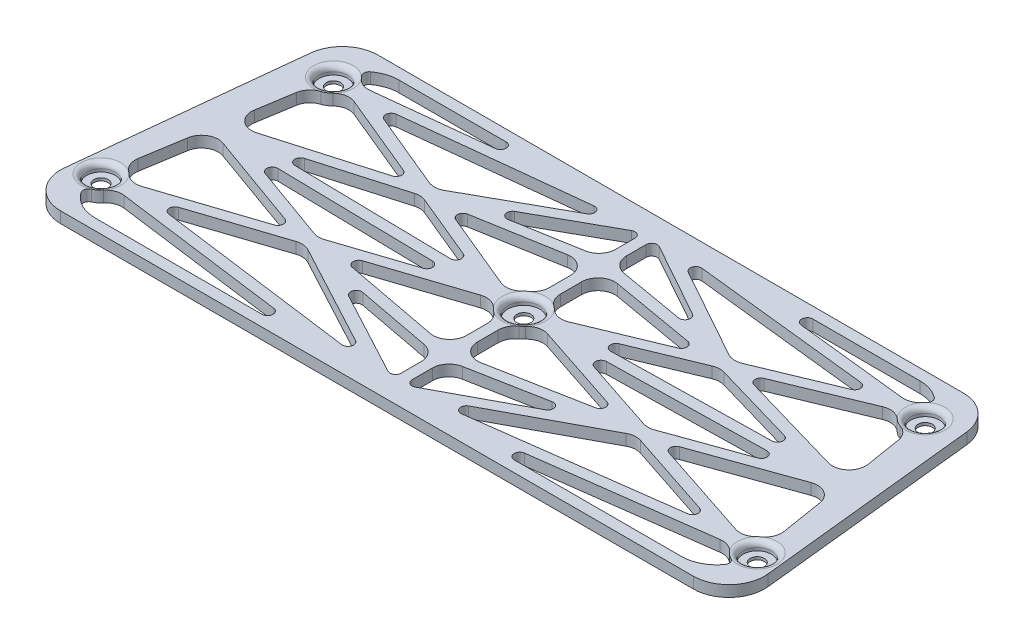
SolidWorks part; units mm, degrees
ref_plane "Front Plane" through (0, 0, 0) normal (0, 0, 1) x (1, 0, 0)
ref_plane "Top Plane" through (0, 0, 0) normal (0, 1, 0) x (1, 0, 0)
ref_plane "Right Plane" through (0, 0, 0) normal (1, 0, 0) x (0, 0, -1)
sketch "Sketch1" plane through (0, 0, 0) normal (0, 1, 0) x (1, 0, 0)
  line L0 (-101.6, -41.91) -> (-92.71, 41.91)
  line L1 (-101.6, -41.91) -> (101.6, -41.91)
  line L2 (-101.6, -41.91) -> (-101.6, 41.91)
  line L3 (-101.6, 41.91) -> (101.6, 41.91)
  line L4 (101.6, -41.91) -> (101.6, 41.91)
  line L5 (-101.6, -41.91) -> (101.6, 41.91) construction
  line L6 (-101.6, 41.91) -> (101.6, -41.91) construction
  line L7 (0, 41.91) -> (0, -41.91) construction
  line L8 (101.6, -41.91) -> (92.71, 41.91)
  circle A0 centre (0, 0) radius 2.032
  circle A1 centre (-93.6752, -27.0205) radius 2.032
  circle A2 centre (-84.4677, 30.1295) radius 2.032
  circle A3 centre (93.6752, -27.0205) radius 2.032
  circle A4 centre (84.4677, 30.1295) radius 2.032
  point P0 (0, 0)
  dimension "D1" = 4.064
  dimension "D6" = 4.064
  dimension "D2" = 203.2
  dimension "D3" = 83.82
  dimension "D4" = 8.89
  dimension "D5" = 83.946
  dimension "D7" = 14.8895
  dimension "D8" = 7.9248
  dimension "D9" = 57.15
  dimension "D10" = 9.2075
extrude "platw" add sketch "Sketch1" along normal blind 3.175 contours L1 L8 L3 L0 A3 A2 A1 A0 A4 region at (-94.9692, 0, 0.2318)
fillet "Fillet1" radius 10.16 2 edges at (101.6, 1.5875, 41.91) (-101.6, 1.5875, 41.91)
fillet "Fillet2" radius 10.16 2 edges at (-92.71, 1.5875, -41.91) (92.71, 1.5875, -41.91)
sketch "Sketch2" plane through (0, 3.175, 0) normal (0, 1, 0) x (1, 0, 0)
  circle A0 centre (-84.4677, 30.1295) radius 4.064
  circle A1 centre (-93.6752, -27.0205) radius 4.064
  circle A2 centre (93.6752, -27.0205) radius 4.064
  circle A3 centre (84.4677, 30.1295) radius 4.064
  circle A4 centre (0, 0) radius 4.572
  dimension "D1" = 8.128
  dimension "D2" = 9.144
extrude "countersinks" cut sketch "Sketch2" against normal blind 2.3813
sketch "Sketch3" plane through (0, 3.175, 0) normal (0, 1, 0) x (1, 0, 0)
  line L0 (-88.0237, -27.0205) -> (-6.1595, 0) construction
  line L1 (-47.0916, -13.5103) -> (-89.0714, 1.5545) construction
  line L2 (-88.0237, -27.0205) -> (0, -38.735) construction
  line L3 (-47.0916, -13.5103) -> (0, -22.4472) construction
  line L4 (-84.4677, 30.1295) -> (-93.6752, -27.0205)
  line L5 (-83.697, -38.735) -> (83.697, -38.735)
  line L6 (93.6752, -27.0205) -> (84.4677, 30.1295)
  line L7 (-74.3648, 38.735) -> (74.3648, 38.735)
  line L8 (-90.3054, -41.91) -> (90.3054, -41.91) construction
  line L9 (-83.5706, 41.91) -> (83.5706, 41.91) construction
  line L10 (-78.8162, 30.1295) -> (-6.1595, 0) construction
  line L11 (-47.0916, -13.5103) -> (0, -38.735) construction
  line L12 (-89.3283, -0.04) -> (-51.9664, -13.4475)
  line L13 (0, -38.735) -> (0, -6.1595)
  line L14 (0, 6.1595) -> (0, 38.735)
  line L15 (-78.8162, 30.1295) -> (0, 38.735) construction
  line L16 (0, 22.4473) -> (-42.4878, 15.0647) construction
  line L17 (-42.4878, 15.0647) -> (0, 38.735) construction
  line L18 (-6.1595, 0) -> (-89.0714, 1.5545) construction
  line L19 (-89.0714, 1.5545) -> (-42.4878, 15.0647) construction
  line L20 (-51.9664, -13.4475) -> (-88.2537, -25.4247)
  line L21 (-79.4439, -0.2138) -> (-47.07, -11.8314)
  line L22 (-47.07, -11.8314) -> (-15.5041, -1.4126)
  line L23 (-15.5041, -1.4126) -> (-79.4439, -0.2138)
  line L24 (-40.7674, -13.0946) -> (-5.9476, -1.6018)
  line L25 (-40.7674, -13.0946) -> (-1.5875, -20.5301)
  line L26 (-1.5875, -20.5301) -> (-1.5875, -5.9514)
  line L27 (-80.9563, -26.3596) -> (-8.4517, -36.0087)
  line L28 (-8.4517, -36.0087) -> (-47.2408, -15.2312)
  line L29 (-47.2408, -15.2312) -> (-80.9563, -26.3596)
  line L30 (-12.0338, -38.735) -> (-88.2467, -28.5923)
  line L31 (-37.213, -17.0008) -> (-1.5875, -36.0837)
  line L32 (-1.5875, -36.0837) -> (-1.5875, -23.7618)
  line L33 (-1.5875, -23.7618) -> (-37.213, -17.0008)
  line L34 (-79.0394, 31.702) -> (-14.626, 38.735)
  line L35 (-72.4873, 29.2236) -> (-7.6222, 36.3058)
  line L36 (-7.6222, 36.3058) -> (-42.5894, 16.8254)
  line L37 (-42.5894, 16.8254) -> (-72.4873, 29.2236)
  line L38 (-79.0534, 28.5093) -> (-47.2721, 15.3301)
  line L39 (-47.2721, 15.3301) -> (-88.7921, 3.2884)
  line L40 (-78.576, 2.9455) -> (-42.581, 13.3848)
  line L41 (-42.581, 13.3848) -> (-14.5103, 1.7443)
  line L42 (-14.5103, 1.7443) -> (-78.576, 2.9455)
  line L46 (0, 41.91) -> (0, -41.91) construction
  line L60 (-5.9405, 1.6278) -> (-36.829, 14.4367)
  line L61 (-36.829, 14.4367) -> (-1.5875, 20.5601)
  line L62 (-1.5875, 20.5601) -> (-1.5875, 5.9514)
  line L63 (-33.5443, 18.23) -> (-1.5875, 23.7827)
  line L64 (-1.5875, 23.7827) -> (-1.5875, 36.0334)
  line L65 (-1.5875, 36.0334) -> (-33.5443, 18.23)
  arc A0 (-79.0394, 31.702) -> (-82.063, 35.2439) centre (-84.4677, 30.1295) ccw
  arc A1 (-85.3666, 24.5499) -> (-79.0534, 28.5093) centre (-84.4677, 30.1295) ccw
  arc A4 (-84.4677, 30.1295) -> (-74.3648, 38.735) centre (-74.3648, 28.5018) cw
  arc A5 (74.3648, 38.735) -> (84.4677, 30.1295) centre (74.3648, 28.5018) cw
  arc A6 (-93.6752, -27.0205) -> (-83.697, -38.735) centre (-83.697, -28.6281) ccw
  arc A7 (83.697, -38.735) -> (93.6752, -27.0205) centre (83.697, -28.6281) ccw
  arc A9 (-92.7763, -21.441) -> (-88.2467, -28.5923) centre (-93.6752, -27.0205) cw
  arc A10 (-88.2467, -28.5923) -> (-92.9783, -32.6289) centre (-93.6752, -27.0205) cw
  circle A13 centre (0, 0) radius 6.1595
  point P24 (0, 0)
  point P25 (0, 0)
  point P29 (-52.6286, -12.8834)
  point P38 (-88.2587, -28.6281)
  point P69 (0, 0)
  point P73 (-1.5875, -13.2408)
  dimension "D3" = 12.319
  dimension "D4" = 5.6515
  dimension "D5" = 5.6515
  dimension "D1" = 3.175
  dimension "D2" = 3.175
extrude "pocket 1" cut sketch "Sketch3" against normal through all contours A4 L34 L7 | L37 L36 L35 | L64 L65 L63 | L42 L41 L40 | L39 L38 L4 | L62 L61 L60 | L22 L23 L21 | L20 L12 L4 | L28 L29 L27 | L32 L33 L31 | L25 L26 L24 | A6 L5 L30 region at (-73.0435, 3.175, -15.9243) region at (-58.1721, 3.175, -36.3358) region at (-77.871, 3.175, 13.1847) region at (-64.1002, 3.175, 35.2582) region at (-13.8195, 3.175, -12.03) region at (-15.1255, 3.175, 11.6139) region at (-47.3393, 3.175, 4.4859) region at (-45.5496, 3.175, 25.8665) region at (-13.4627, 3.175, 25.6155) region at (-40.8996, 3.175, -27.4516) region at (-45.2224, 3.175, -6.0249) region at (-12.2398, 3.175, -26.0154)
fillet "acute angles" radius 1.5875 20 edges at (-1.5875, 1.5875, -36.0334) (-33.5443, 1.5875, -18.23) (-14.626, 1.5875, -38.735) (-7.6222, 1.5875, -36.3058) (-72.4873, 1.5875, -29.2236) (-47.2721, 1.5875, -15.3301) (-36.829, 1.5875, -14.4367) (-14.5103, 1.5875, -1.7443) (-78.576, 1.5875, -2.9455) (-12.0338, 1.5875, 38.735) (-8.4517, 1.5875, 36.0087) (-1.5875, 1.5875, 36.0837) (-37.213, 1.5875, 17.0008) (-51.9664, 1.5875, 13.4475) (-40.7674, 1.5875, 13.0946) (-15.5041, 1.5875, 1.4126) (-79.4439, 1.5875, 0.2138) (-80.9563, 1.5875, 26.3596) (-92.9783, 1.5875, 32.6289) (-82.063, 1.5875, -35.2439)
fillet "Fillet5" radius 4.7625 20 edges at (-1.5875, 1.5875, -20.5601) (-1.5875, 1.5875, -23.7827) (-42.5894, 1.5875, -16.8254) (-42.581, 1.5875, -13.3848) (-88.7921, 1.5875, -3.2884) (-1.5875, 1.5875, 23.7618) (-1.5875, 1.5875, 20.5301) (-47.2408, 1.5875, 15.2312) (-47.07, 1.5875, 11.8314) (-89.3283, 1.5875, 0.04) (-1.5875, 1.5875, 5.9514) (-5.9476, 1.5875, 1.6018) (-88.2467, 1.5875, 28.5923) (-88.2537, 1.5875, 25.4247) (-92.7763, 1.5875, 21.441) (-5.9405, 1.5875, -1.6278) (-1.5875, 1.5875, -5.9514) (-85.3666, 1.5875, -24.5499) (-79.0534, 1.5875, -28.5093) (-79.0394, 1.5875, -31.702)
ref_plane "Plane1" through (0, 0, 0) normal (-1, 0, 0) x (0, 0, 1)
mirror "Mirror1" about plane through (0, 0, 0) normal (-1, 0, 0) of "Fillet5", "acute angles", "pocket 1"
fillet "Fillet6" radius 1.5875 5 edges at (84.4677, 3.175, -26.0655) (93.6752, 3.175, 31.0845) (-93.6752, 3.175, 31.0845) (-84.4677, 3.175, -26.0655) (0, 3.175, 4.572)
equation "\"q1\" = .0625"
